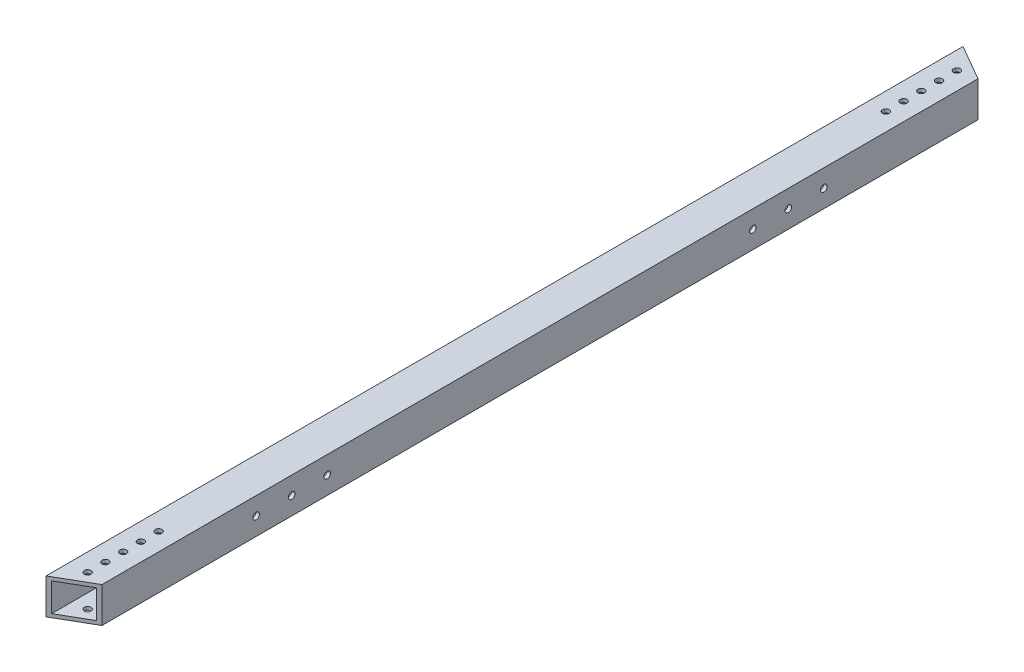
SolidWorks part; units mm, degrees
ref_plane "Front Plane" through (0, 0, 0) normal (0, 0, 1) x (1, 0, 0)
ref_plane "Top Plane" through (0, 0, 0) normal (0, 1, 0) x (1, 0, 0)
ref_plane "Right Plane" through (0, 0, 0) normal (1, 0, 0) x (0, 0, -1)
sketch "Sketch1" plane through (0, 0, 0) normal (0, 0, 1) x (1, 0, 0)
  line L0 (-10.16, 10.16) -> (10.16, 10.16)
  line L1 (-12.7, -12.7) -> (12.7, -12.7)
  line L2 (-12.7, -12.7) -> (-12.7, 12.7)
  line L3 (-12.7, 12.7) -> (12.7, 12.7)
  line L4 (12.7, -12.7) -> (12.7, 12.7)
  line L5 (-12.7, -12.7) -> (12.7, 12.7) construction
  line L6 (-12.7, 12.7) -> (12.7, -12.7) construction
  line L7 (10.16, -10.16) -> (10.16, 10.16)
  line L8 (-10.16, -10.16) -> (10.16, -10.16)
  line L9 (-10.16, -10.16) -> (-10.16, 10.16)
  point P0 (0, 0)
  dimension "D1" = 25.4
  dimension "D2" = 25.4
  dimension "D3" = 2.54
extrude "Boss-Extrude2" add sketch "Sketch1" along normal blind 656.5743
sketch "Sketch2" plane through (0, 12.7, 0) normal (0, 1, 0) x (1, 0, 0)
  line L0 (-12.7, -656.5743) -> (12.7, -641.9096)
  line L1 (12.7, -656.5743) -> (12.7, 0) construction
  line L2 (12.7, -641.9096) -> (12.7, -656.5743)
  line L3 (12.7, -656.5743) -> (-12.7, -656.5743)
  line L4 (-12.7, -328.2872) -> (12.7, -328.2872) construction
  line L5 (-12.7, -656.5743) -> (-12.7, 0) construction
  line L6 (12.7, 0) -> (-12.7, 0)
  line L7 (12.7, -14.6647) -> (12.7, 0)
  line L8 (-12.7, 0) -> (12.7, -14.6647)
  dimension "D1" = 30
extrude "Cut-Extrude1" cut sketch "Sketch2" against normal through all
sketch "Sketch3" plane through (0, 12.7, 0) normal (0, 1, 0) x (1, 0, 0)
  line L0 (0, -7.3323) -> (0, -649.242) construction
  line L1 (-12.7, 0) -> (12.7, -14.6647) construction
  line L2 (12.7, -641.9096) -> (-12.7, -656.5743) construction
  line L3 (12.7, -328.2872) -> (-12.7, -328.2872) construction
  line L4 (12.7, -641.9096) -> (12.7, -14.6647) construction
  line L5 (-12.7, -656.5743) -> (-12.7, 0) construction
  circle A5 centre (0, -639.4372) radius 2.3813
  circle A6 centre (0, -626.7372) radius 2.3813
  circle A7 centre (0, -614.0372) radius 2.3813
  circle A8 centre (0, -601.3372) radius 2.3813
  circle A9 centre (0, -588.6372) radius 2.3813
  circle A10 centre (0, -67.9372) radius 2.3812
  circle A11 centre (0, -55.2372) radius 2.3812
  circle A12 centre (0, -42.5372) radius 2.3812
  circle A13 centre (0, -29.8372) radius 2.3813
  circle A14 centre (0, -17.1372) radius 2.3813
  dimension "D3" = 4.7625
  dimension "D5" = 5
extrude "Cut-Extrude2" cut sketch "Sketch3" against normal through all
sketch "Sketch4" plane through (-12.7, 0, 0) normal (-1, 0, 0) x (0, 0, 1)
  line L0 (0, 0) -> (656.5743, 0) construction
  line L1 (656.5743, 12.7) -> (656.5743, -12.7) construction
  line L2 (328.2872, 12.7) -> (328.2872, -12.7) construction
  line L3 (656.5743, 12.7) -> (0, 12.7) construction
  line L4 (656.5743, -12.7) -> (0, -12.7) construction
  circle A0 centre (175.8872, 0) radius 2.3813
  circle A1 centre (150.4872, 0) radius 2.3813
  circle A2 centre (125.0872, 0) radius 2.3813
  circle A3 centre (531.4872, 0) radius 2.3812
  circle A4 centre (506.0872, 0) radius 2.3813
  circle A5 centre (480.6872, 0) radius 2.3812
  dimension "D1" = 4.7625
  dimension "D2" = 152.4
  dimension "D3" = 3
extrude "Cut-Extrude3" cut sketch "Sketch4" against normal through all
